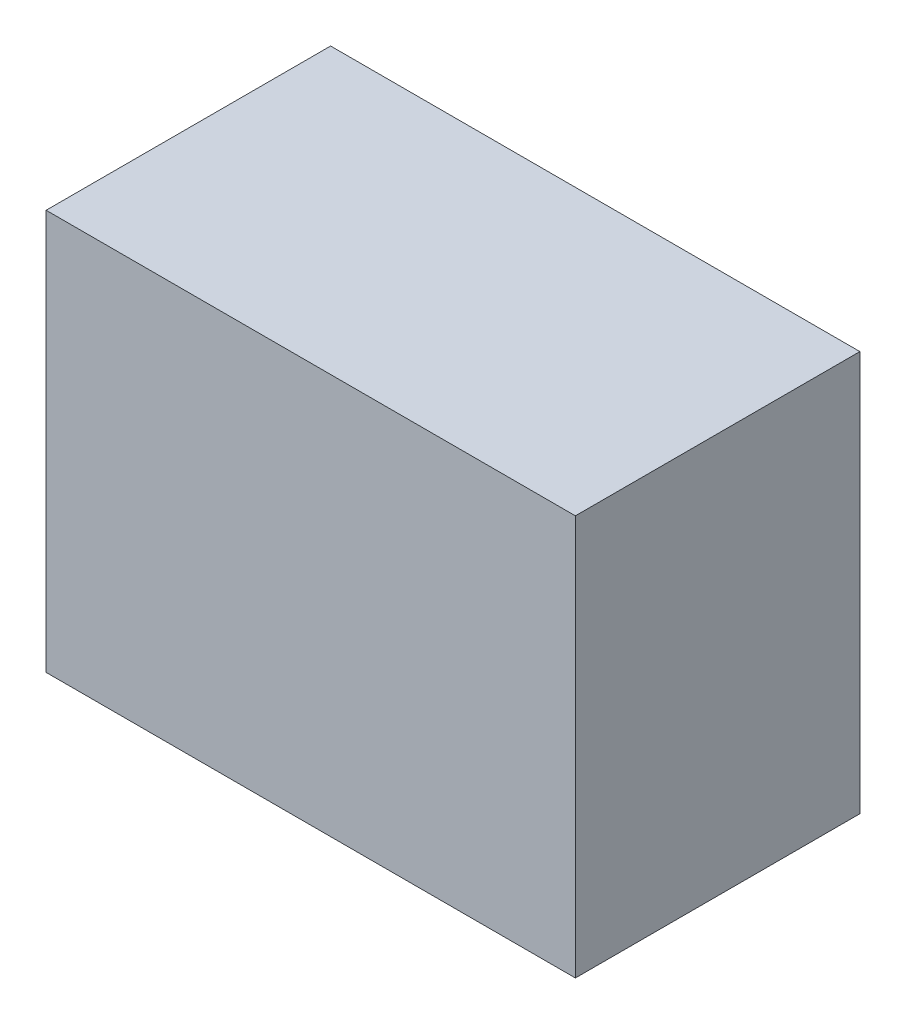
SolidWorks part; units mm, degrees
ref_plane "Front Plane" through (0, 0, 0) normal (0, 0, 1) x (1, 0, 0)
ref_plane "Top Plane" through (0, 0, 0) normal (0, 1, 0) x (1, 0, 0)
ref_plane "Right Plane" through (0, 0, 0) normal (1, 0, 0) x (0, 0, -1)
sketch "Sketch2" plane through (0, 0, 0) normal (0, 1, 0) x (1, 0, 0)
  line L1 (-160, -86) -> (160, -86)
  line L2 (-160, -86) -> (-160, 86)
  line L3 (-160, 86) -> (160, 86)
  line L4 (160, -86) -> (160, 86)
  line L5 (-160, -86) -> (160, 86) construction
  line L6 (-160, 86) -> (160, -86) construction
  point P0 (0, 0)
  dimension "D1" = 320
  dimension "D2" = 172
extrude "Boss-Extrude1" add sketch "Sketch2" along normal blind 242
equation "\"PCWidth\"= 172mm"
equation "\"PCLength\"= 320mm"
equation "\"PCHeight\"= 242mm"
equation "\"WallThickness\"= 9mm"
equation "\"ThermoBarrierThickness\"= 3mm"
equation "\"HotSideGap\"= 50mm"
equation "\"D1@Boss-Extrude1\"=\"PCHeight\""
equation "\"D1@Sketch2\"=\"PCLength\""
equation "\"D2@Sketch2\"=\"PCWidth\""
